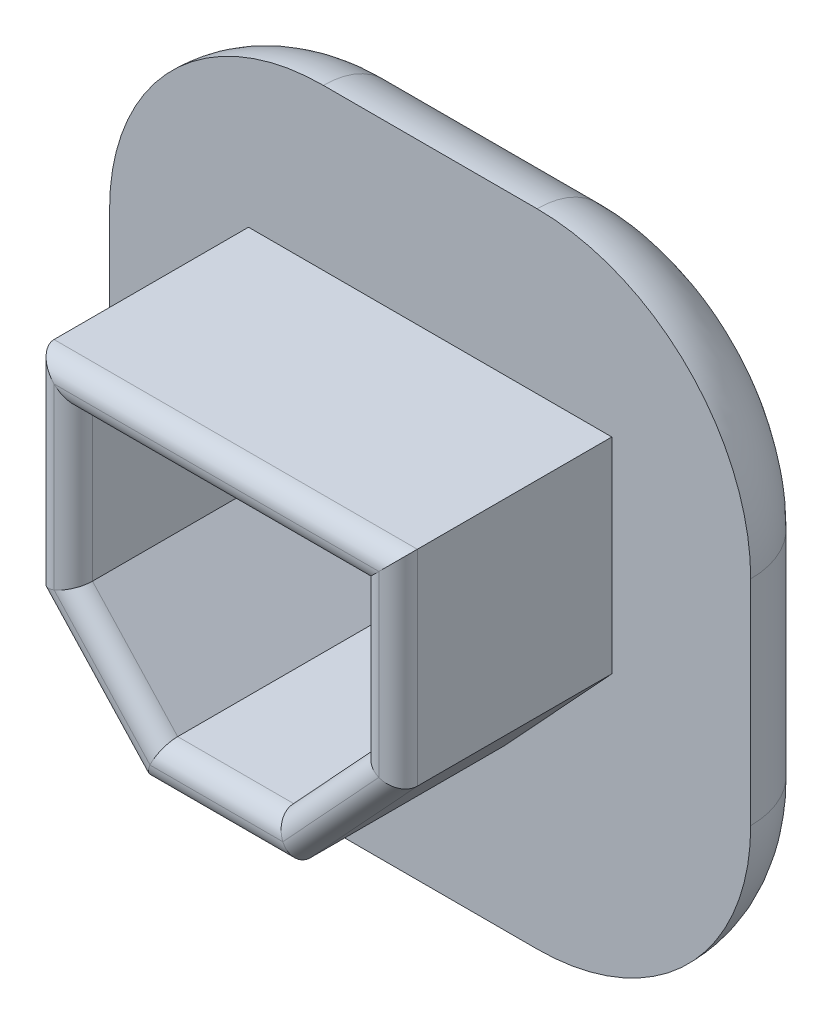
SolidWorks part; units mm, degrees
ref_plane "Front Plane" through (0, 0, 0) normal (0, 0, 1) x (1, 0, 0)
ref_plane "Top Plane" through (0, 0, 0) normal (0, 1, 0) x (1, 0, 0)
ref_plane "Right Plane" through (0, 0, 0) normal (1, 0, 0) x (0, 0, -1)
sketch "Sketch1" plane through (0, 0, 0) normal (0, 0, 1) x (1, 0, 0)
  line L1 (-7.5, -7.5) -> (7.5, -7.5)
  line L2 (-7.5, -7.5) -> (-7.5, 7.5)
  line L3 (-7.5, 7.5) -> (7.5, 7.5)
  line L4 (7.5, -7.5) -> (7.5, 7.5)
  line L5 (-7.5, -7.5) -> (7.5, 7.5) construction
  line L6 (-7.5, 7.5) -> (7.5, -7.5) construction
  point P0 (0, 0)
  dimension "D1" = 15
  dimension "D2" = 15
extrude "Boss-Extrude1" add sketch "Sketch1" along normal blind 2
fillet "Fillet11" radius 5 4 edges at (7.5, -7.5, 1) (-7.5, -7.5, 1) (-7.5, 7.5, 1) (7.5, 7.5, 1)
fillet "Fillet13" radius 2 8 edges at (6.0355, 6.0355, 0) (0, 7.5, 0) (-6.0355, 6.0355, 0) (-7.5, 0, 0) (-6.0355, -6.0355, 0) (0, -7.5, 0) (6.0355, -6.0355, 0) (7.5, 0, 0)
sketch "Sketch7" plane through (0, 0, 2) normal (0, 0, 1) x (1, 0, 0)
  line L1 (-4.25, -3.75) -> (4.25, -3.75)
  line L2 (-4.25, -3.75) -> (-4.25, 3.75)
  line L3 (-4.25, 3.75) -> (4.25, 3.75)
  line L4 (4.25, -3.75) -> (4.25, 3.75)
  line L5 (-4.25, -3.75) -> (4.25, 3.75) construction
  line L6 (-4.25, 3.75) -> (4.25, -3.75) construction
  point P0 (0, 0)
  dimension "D1" = 8.5
  dimension "D2" = 7.5
extrude "Boss-Extrude5" add sketch "Sketch7" along normal blind 5
sketch "Sketch8" plane through (0, 0, 7) normal (0, 0, 1) x (1, 0, 0)
  line L0 (-4.25, -1.05) -> (-1.75, -3.75)
  line L1 (-4.25, 3.75) -> (-4.25, -3.75) construction
  line L2 (-4.25, -3.75) -> (4.25, -3.75) construction
  line L3 (-1.75, -3.75) -> (-4.25, -3.75)
  line L4 (-4.25, -3.75) -> (-4.25, -1.05)
  line L5 (4.25, -1.05) -> (1.75, -3.75)
  line L6 (4.25, -3.75) -> (4.25, 3.75) construction
  line L7 (1.75, -3.75) -> (4.25, -3.75)
  line L8 (4.25, -3.75) -> (4.25, -1.05)
  dimension "D1" = 4.8
  dimension "D2" = 4.8
  dimension "D3" = 2.5
  dimension "D4" = 2.5
extrude "Cut-Extrude3" cut sketch "Sketch8" against normal blind 5
shell "Shell8" thickness 0.9 removed face at (0, -0.35, 7)
fillet "Fillet15" radius 0.45 12 edges at (-2.3534, -1.7737, 7) (0, -2.85, 7) (2.3534, -1.7737, 7) (3.35, 1.0763, 7) (0, 2.85, 7) (-3.35, 1.0763, 7) (0, 3.75, 7) (4.25, 1.35, 7) (3, -2.4, 7) (0, -3.75, 7) (-3, -2.4, 7) (-4.25, 1.35, 7)
